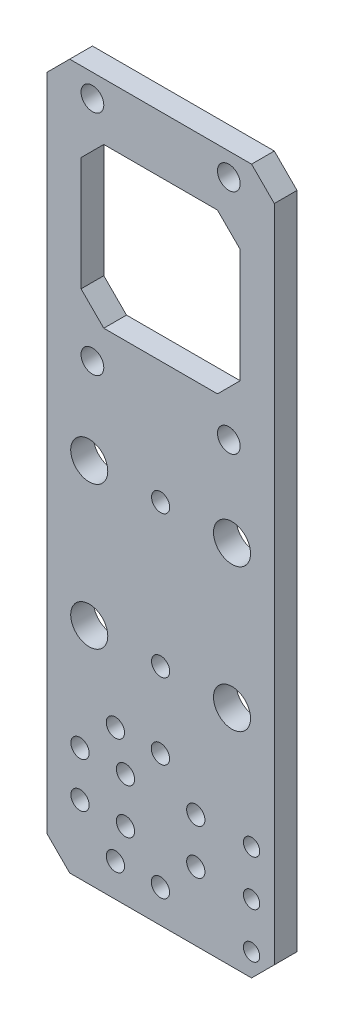
SolidWorks part; units mm, degrees
ref_plane "Front Plane" through (0, 0, 0) normal (0, 0, 1) x (1, 0, 0)
ref_plane "Top Plane" through (0, 0, 0) normal (0, 1, 0) x (1, 0, 0)
ref_plane "Right Plane" through (0, 0, 0) normal (1, 0, 0) x (0, 0, -1)
sketch "Sketch1" plane through (0, 0, 0) normal (0, 0, 1) x (1, 0, 0)
  line L1 (-31.75, -82.55) -> (31.75, -82.55)
  line L2 (-31.75, -82.55) -> (-31.75, 114.3)
  line L3 (-31.75, 114.3) -> (31.75, 114.3)
  line L4 (31.75, -82.55) -> (31.75, 114.3)
  line L5 (-31.75, -82.55) -> (31.75, 114.3) construction
  line L6 (-31.75, 114.3) -> (31.75, -82.55) construction
  point P0 (0, 0)
  point P6 (0, 0)
  point P7 (0, 114.3)
  point P8 (0, 0)
  dimension "D1" = 82.55
  dimension "D2" = 63.5
  dimension "D3" = 114.3
extrude "Boss-Extrude1" add sketch "Sketch1" along normal mid plane 6.35
sketch "Sketch2" plane through (0, 0, 3.175) normal (0, 0, 1) x (1, 0, 0)
  line L0 (31.75, 114.3) -> (-31.75, 114.3) construction
  line L1 (-19.939, 19.939) -> (19.939, 19.939) construction
  line L2 (-19.939, 19.939) -> (-19.939, -19.939) construction
  line L3 (-19.939, -19.939) -> (19.939, -19.939) construction
  line L4 (19.939, 19.939) -> (19.939, -19.939) construction
  line L5 (-19.939, 19.939) -> (19.939, -19.939) construction
  line L6 (-19.939, -19.939) -> (19.939, 19.939) construction
  line L9 (0, -19.85) -> (0, 19.85) construction
  circle A8 centre (-19.939, -19.939) radius 2 construction
  circle A9 centre (19.939, -19.939) radius 2 construction
  circle A10 centre (19.939, 19.939) radius 2 construction
  circle A11 centre (-19.939, 19.939) radius 2 construction
  arc A13 (2.5159, 20.1991) -> (2.5158, 20.2) centre (0, 19.85) ccw
  circle A14 centre (0, -19.85) radius 2.54
  circle A17 centre (0, 19.85) radius 2.54
  circle A18 centre (-19.939, 19.939) radius 5.175
  circle A19 centre (19.939, 19.939) radius 5.175
  circle A20 centre (19.939, -19.939) radius 5.175
  circle A21 centre (-19.939, -19.939) radius 5.175
  point P1 (-19.9233, 36.5332)
  point P3 (0, 0)
  point P4 (0, 0)
  point P5 (0, 0)
  point P7 (0, 0)
  point P8 (-4.4024, 12.1093)
  point P9 (0, 0)
  point P15 (0, 0)
  point P35 (0, 114.3)
  point P36 (6.0416, 14.1072)
  point P40 (0, 0)
  dimension "D5" = 10.35
  dimension "D4" = 5.08
  dimension "D2" = 39.878
  dimension "D3" = 39.7
  dimension "D1" = 3.175
extrude "Cut-Extrude1" cut sketch "Sketch2" against normal through all contours A11 | A10 | A13 A17 | A9 | A14 | A8 | A18 | A21 | A20 | A19 region at (0, 19.85, 3.175) region at (0, -19.85, 3.175) region at (-19.939, 19.939, 3.175) region at (19.939, 19.939, 3.175) region at (19.939, -19.939, 3.175) region at (-19.939, -19.939, 3.175)
sketch "Sketch3" plane through (0, 0, 3.175) normal (0, 0, 1) x (1, 0, 0)
  line L0 (31.75, 114.3) -> (-31.75, 114.3) construction
  line L1 (-22.225, 53.975) -> (22.225, 53.975)
  line L2 (-22.225, 53.975) -> (-22.225, 98.425)
  line L3 (-22.225, 98.425) -> (22.225, 98.425)
  line L4 (22.225, 53.975) -> (22.225, 98.425)
  line L5 (-22.225, 53.975) -> (22.225, 98.425) construction
  line L6 (-22.225, 98.425) -> (22.225, 53.975) construction
  point P0 (0, 76.2)
  point P5 (-1.8062, 54.4045)
  point P6 (1.5658, 47.3141)
  point P9 (0, 114.3)
  point P10 (0, 56.243)
  dimension "D1" = 44.45
  dimension "D2" = 38.1
extrude "Cut-Extrude2" cut sketch "Sketch3" against normal through all
sketch "Sketch4" plane through (0, 0, 3.175) normal (0, 0, 1) x (1, 0, 0)
  line L0 (22.225, 98.425) -> (-22.225, 98.425) construction
  line L1 (-19.05, 44.45) -> (19.05, 44.45) construction
  line L2 (-19.05, 44.45) -> (-19.05, 107.95) construction
  line L3 (-19.05, 107.95) -> (19.05, 107.95) construction
  line L4 (19.05, 44.45) -> (19.05, 107.95) construction
  line L5 (-19.05, 44.45) -> (19.05, 107.95) construction
  line L6 (-19.05, 107.95) -> (19.05, 44.45) construction
  line L7 (-22.225, 98.425) -> (-22.225, 53.975) construction
  circle A0 centre (-19.05, 107.95) radius 3.175
  circle A1 centre (19.05, 107.95) radius 3.175
  circle A2 centre (19.05, 44.45) radius 3.175
  circle A3 centre (-19.05, 44.45) radius 3.175
  point P8 (0, 76.2)
  point P9 (0, 0)
  point P11 (0, 0)
  point P12 (0, 0)
  point P15 (0, 98.425)
  point P18 (-22.225, 76.2)
  point P19 (29.0563, 104.3064)
  point P20 (0, 0)
  dimension "D3" = 6.35
  dimension "D1" = 38.1
  dimension "D2" = 63.5
extrude "Cut-Extrude3" cut sketch "Sketch4" against normal through all
chamfer "Chamfer1" distance 6.35 angle 45 8 edges at (31.75, -82.55, 0) (-31.75, -82.55, 0) (31.75, 114.3, 0) (-31.75, 114.3, 0) (-22.225, 53.975, 0) (22.225, 53.975, 0) (22.225, 98.425, 0) (-22.225, 98.425, 0)
sketch "Sketch5" plane through (0, 0, -3.175) normal (0, 0, -1) x (-1, 0, 0)
  line L0 (-25.4, -50.8) -> (-25.4, -63.5) construction
  line L1 (-25.4, -63.5) -> (-25.4, -76.2) construction
  line L2 (25.4, -82.55) -> (-25.4, -82.55) construction
  line L3 (-31.75, -76.2) -> (-31.75, 107.95) construction
  circle A0 centre (-25.4, -50.8) radius 2.286
  circle A1 centre (-25.4, -63.5) radius 2.286
  circle A2 centre (-25.4, -76.2) radius 2.286
  dimension "D1" = 4.572
  dimension "D2" = 6.35
  dimension "D3" = 12.7
  dimension "D4" = 6.35
extrude "Cut-Extrude4" cut sketch "Sketch5" against normal through all
sketch "Sketch6" plane through (0, 0, 3.175) normal (0, 0, 1) x (1, 0, 0)
  line L0 (-22.5145, -50.8638) -> (-12.6362, -40.9855) construction
  line L1 (-22.5145, -50.8638) -> (-0.0638, -73.3145) construction
  line L2 (-12.6362, -40.9855) -> (9.8145, -63.4362) construction
  line L3 (-0.0638, -73.3145) -> (9.8145, -63.4362) construction
  line L4 (-12.6362, -40.9855) -> (-0.0638, -73.3145) construction
  line L5 (-25.4, -82.55) -> (25.4, -82.55) construction
  line L7 (-31.75, 107.95) -> (-31.75, -76.2) construction
  point P2 (-6.35, -57.15)
  point P3 (9.8145, -63.4362)
  point P5 (-12.6362, -40.9855)
  point P6 (-22.5145, -50.8638)
  point P7 (-0.0638, -73.3145)
  point P13 (4.8753, -68.3753)
  point P14 (-17.5753, -45.9247)
  point P15 (-11.2891, -62.0891)
  point P16 (-1.4109, -52.2109)
  point P17 (0, 0)
  dimension "D1" = 25.4
  dimension "D2" = 31.75
  dimension "D3" = 13.97
  dimension "D4" = 25.4
  dimension "D5" = 45
hole_wizard "#10 Clearance Hole1" positions "Sketch7" profile "Sketch8" hole size "#10" standard "ANSI Inch"
sketch "Sketch7" plane through (0, 0, 3.175) normal (0, 0, 1) x (1, 0, 0)
  point P0 (-22.5145, -50.8638)
  point P3 (-12.6362, -40.9855)
  point P6 (9.8145, -63.4362)
  point P9 (-0.0638, -73.3145)
sketch "Sketch8" plane through (-22.5145, -50.8638, 3.175) normal (1, 0, 0) x (0, -1, 0)
  line L0 (0, 0) -> (0, 20.5838)
  line L1 (0, 20.5838) -> (2.5527, 19.05)
  line L2 (2.5527, 19.05) -> (2.5527, 0)
  line L5 (2.5527, 0) -> (0, 0)
  line L10 (0, 20.5838) -> (-2.5527, 19.05) construction
  line L11 (0, -6.35) -> (0, 107.95) construction
  dimension "Hole Dia." = 5.1054
  dimension "Hole Depth" = 19.05
  dimension "Drill Angle" = 118
ref_plane "Plane1" through (-6.35, 0, 0) normal (-1, 0, 0) x (0, 0, 1)
mirror "Mirror1" about plane through (-6.35, 0, 0) normal (-1, 0, 0) of "#10 Clearance Hole1"
sketch "Sketch9" plane through (0, 0, 3.175) normal (0, 0, 1) x (1, 0, 0)
  circle A0 centre (-9.8145, -50.8638) radius 2.5527
  circle A1 centre (-9.8145, -63.4362) radius 2.5527
  circle A2 centre (-22.5145, -50.8638) radius 2.5527 construction
  point P4 (-22.5145, -63.4362)
  point P5 (0, 0)
  point P8 (0, 0)
  point P9 (0, 0)
  point P10 (0, 0)
  dimension "D1" = 12.7
extrude "Cut-Extrude6" cut sketch "Sketch9" against normal through all
